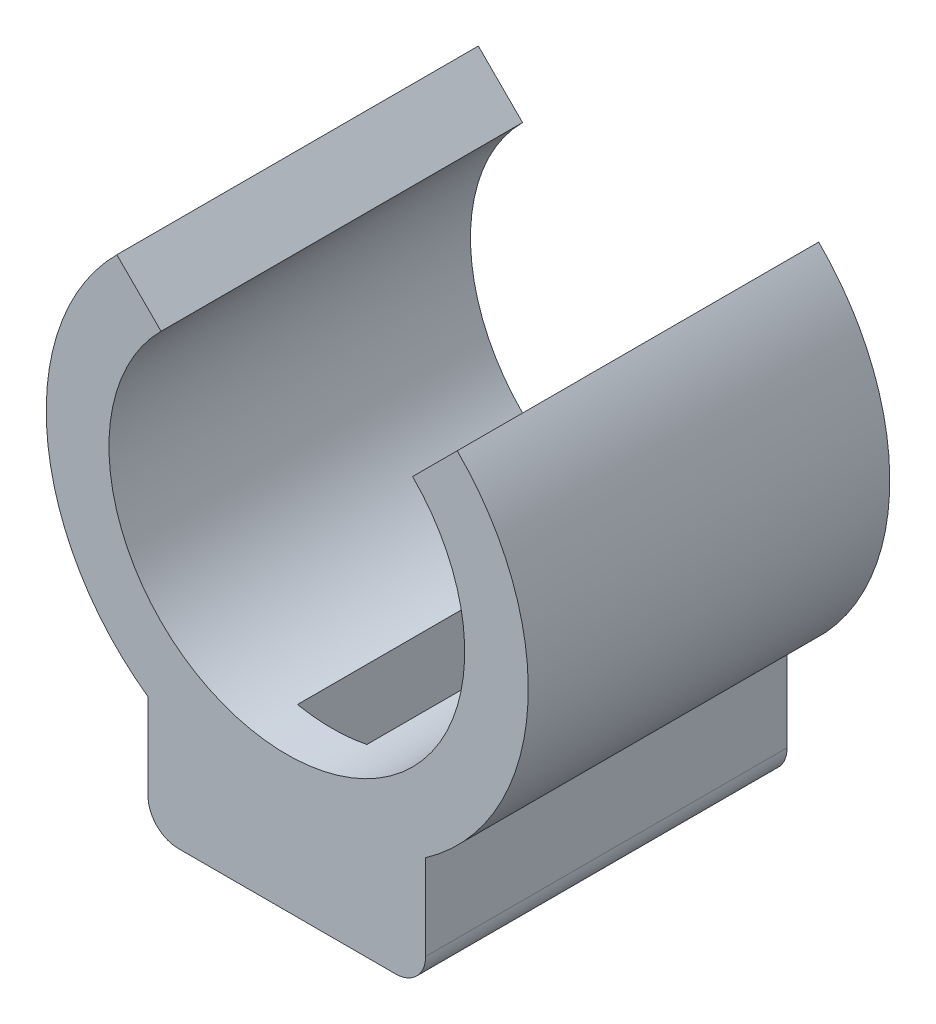
SolidWorks part; units mm, degrees
ref_plane "Front Plane" through (0, 0, 0) normal (0, 0, 1) x (1, 0, 0)
ref_plane "Top Plane" through (0, 0, 0) normal (0, 1, 0) x (1, 0, 0)
ref_plane "Right Plane" through (0, 0, 0) normal (1, 0, 0) x (0, 0, -1)
sketch "Sketch1" plane through (0, 0, 0) normal (0, 1, 0) x (1, 0, 0)
  line L0 (-1.7277, 5.1953) -> (-1.7277, -0.8002)
  line L1 (0, 0) -> (1.15, 0)
  line L2 (0, 0) -> (0, 4.4)
  line L3 (0, 4.4) -> (1.15, 4.4)
  line L4 (1.15, 0) -> (1.15, 4.4)
  line L5 (2.875, 5.1953) -> (2.875, -0.8002)
  line L8 (-1.7277, 5.1953) -> (2.875, 5.1953)
  line L12 (2.875, -0.8002) -> (-1.7277, -0.8002)
extrude "Boss-Extrude1" add sketch "Sketch1" along normal blind 2 and the other way blind 0.2
sketch "Sketch3" plane through (0, 0, 0.8002) normal (0, 0, 1) x (1, 0, 0)
  line L0 (0.5736, 2) -> (0.5736, 5) construction
  line L1 (-1.7277, 2) -> (2.875, 2) construction
  line L2 (2.0736, 6.5) -> (0.5736, 8) construction
  line L3 (-2.2454, 7.8191) -> (-1.5123, 7.086)
  line L4 (3.3996, 7.8259) -> (2.6596, 7.086)
  line L6 (0.5736, 8) -> (-0.9264, 6.5) construction
  arc A0 (-1.5123, 7.086) -> (2.6596, 7.086) centre (0.5736, 5) ccw
  arc A2 (-1.5477, 7.1213) -> (2.695, 7.1213) centre (0.5736, 5) ccw construction
  arc A3 (-2.2454, 7.8191) -> (3.3996, 7.8259) centre (0.5805, 4.9919) ccw
  dimension "D1" = 0.05
extrude "Boss-Extrude2" add sketch "Sketch3" against normal up to surface (5.9955 mm away) up to face at (0.5736, 0.9, -5.1953)
sketch "Sketch4" plane through (0, 0, 0) normal (0, -1, 0) x (1, 0, 0)
  line L1 (0, -4.45) -> (1.15, -4.45)
  line L2 (0, -4.45) -> (0, 0.05)
  line L3 (0, 0.05) -> (1.15, 0.05)
  line L4 (1.15, -4.45) -> (1.15, 0.05)
extrude "Cut-Extrude2" cut sketch "Sketch4" against normal blind 2.2
fillet "Fillet1" radius 0.5 2 edges at (-1.7277, -0.2, -2.1976) (2.875, -0.2, -2.1976)
fillet "Fillet2" radius 0.3 2 edges at (0.575, -0.2, -4.4) (0.575, -0.2, 0)
